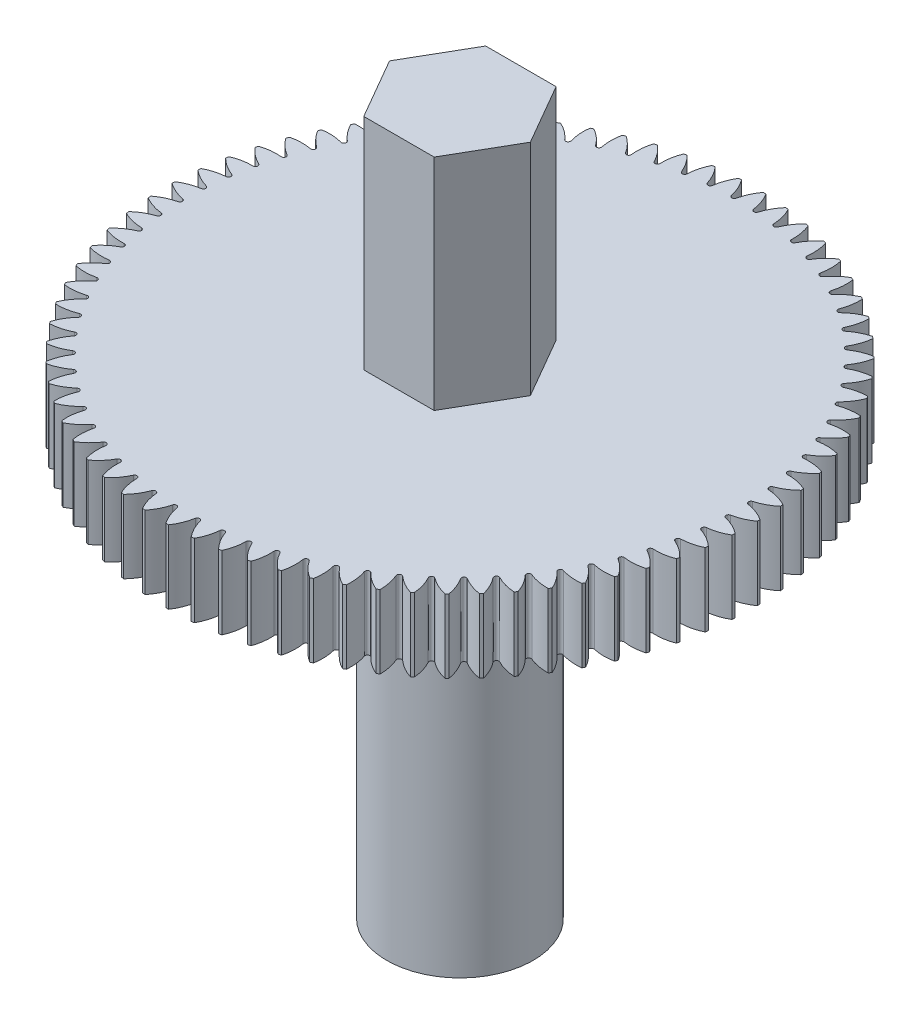
SolidWorks part; units mm, degrees
ref_plane "前视基准面" through (0, 0, 0) normal (0, 0, 1) x (1, 0, 0)
ref_plane "上视基准面" through (0, 0, 0) normal (0, 1, 0) x (1, 0, 0)
ref_plane "右视基准面" through (0, 0, 0) normal (1, 0, 0) x (0, 0, -1)
sketch "草图1" plane through (0, 0, 0) normal (0, 0, 1) x (1, 0, 0)
  line L0 (0, 0) -> (0, 29)
  line L1 (0, 29) -> (3, 29)
  line L2 (3, 29) -> (3, 20)
  line L3 (3, 20) -> (12, 20)
  line L4 (12, 20) -> (12, 17)
  line L5 (12, 17) -> (3, 17)
  line L6 (3, 17) -> (3, 0)
  line L7 (3, 0) -> (0, 0)
  dimension "D1" = 3
  dimension "D2" = 29
  dimension "D3" = 9
  dimension "D4" = 17
  dimension "D5" = 3
revolve "旋转1" add sketch "草图1" angle 360 about L0
sketch "草图2" plane through (0, 20, 0) normal (0, 1, 0) x (1, 0, 0)
  line L0 (0, 0) -> (0, 12) construction
  line L1 (-0.45, 12) -> (0.45, 12)
  circle A0 centre (0, 0) radius 12 construction
  arc A1 (-0.0977, 11.2287) -> (0.0977, 11.2287) centre (0, 11.25) ccw
  arc A2 (0.45, 12) -> (0.0977, 11.2287) centre (2.0517, 10.8023) ccw
  arc A3 (-0.45, 12) -> (-0.0977, 11.2287) centre (-2.0517, 10.8023) cw
  point P8 (0, 12)
  dimension "D2" = 0.2
  dimension "D3" = 4
  dimension "D1" = 0.9
  dimension "D4" = 0.75
extrude "切除-拉伸1" cut sketch "草图2" against normal blind 4
pattern_circular "阵列(圆周)1" count 75 over 360 about axis through (0, 0, 0) along (0, -1, 0) of "切除-拉伸1" reverse direction yes
sketch "草图3" plane through (0, 29, 0) normal (0, 1, 0) x (1, 0, 0)
  line L1 (2.8868, 0) -> (1.4434, 2.5)
  line L2 (1.4434, 2.5) -> (-1.4434, 2.5)
  line L3 (-1.4434, 2.5) -> (-2.8868, 0)
  line L4 (-2.8868, 0) -> (-1.4434, -2.5)
  line L5 (-1.4434, -2.5) -> (1.4434, -2.5)
  line L6 (1.4434, -2.5) -> (2.8868, 0)
  circle A0 centre (0, 0) radius 2.5 construction
  circle A2 centre (0, 0) radius 3 construction
  circle A3 centre (0, 0) radius 3
  dimension "D1" = 5
extrude "切除-拉伸2" cut sketch "草图3" against normal blind 9
